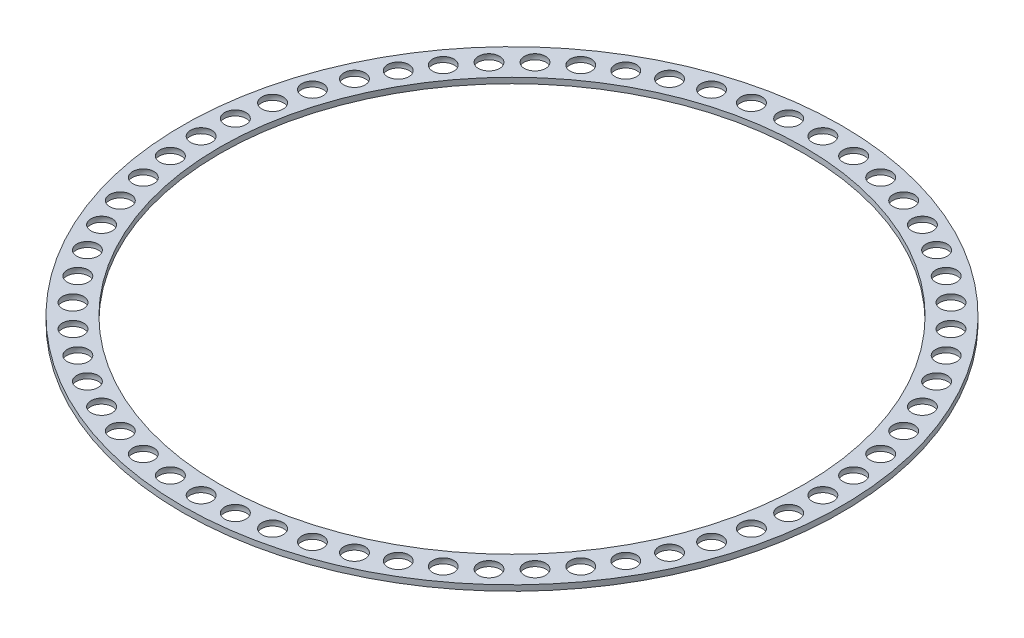
SolidWorks part; units mm, degrees
material "Nylon 6/10"
ref_plane "Front" through (0, 0, 0) normal (0, 0, 1) x (1, 0, 0)
ref_plane "Top" through (0, 0, 0) normal (0, 1, 0) x (1, 0, 0)
ref_plane "Right" through (0, 0, 0) normal (1, 0, 0) x (0, 0, -1)
sketch "Sketch1" plane through (0, 0, 0) normal (0, 1, 0) x (1, 0, 0)
  line L1 (0, 0) -> (-78.05, 0) construction
  line L2 (-78.05, 0) -> (-88.05, 0) construction
  circle A0 centre (0, 0) radius 78.05
  circle A1 centre (0, 0) radius 83.05 construction
  circle A3 centre (0, 0) radius 88.05
  point P6 (-83.05, 0)
  dimension "D1" = 166.1
  dimension "D2" = 10
extrude "Boss-Extrude1" add sketch "Sketch1" along normal blind 1.5
sketch "Sketch2" plane through (0, 0, 0) normal (0, 0, 1) x (1, 0, 0)
  line L0 (83.05, -2.5) -> (83.05, 3.5)
  line L2 (0, 0) -> (83.05, 0) construction
  arc A1 (83.05, 3.5) -> (83.05, -2.5) centre (83.05, 0.5) cw
  point P2 (83.05, 0.5)
  point P3 (92.7788, 0)
  point P5 (0, 0)
  point P6 (0, 0)
  point P9 (83.05, 0.5)
  point P10 (92.6155, 0)
  point P11 (92.2251, 1.6879)
  point P12 (0, 0)
  dimension "D1" = 3
  dimension "D2" = 0.5
  dimension "D3" = 83.05
revolve "Cut-Revolve1" cut sketch "Sketch2" angle 360 about L0
ref_axis "Axis1" through (0, 0, 0) along (0, 1, 0)
pattern_circular "CirPattern5" count 60 over 360 about axis through (0, 0, 0) along (0, 1, 0) of "Cut-Revolve1"
ref_axis "Axis2" through (83.05, -2.5, 0) along (0, 1, 0)
